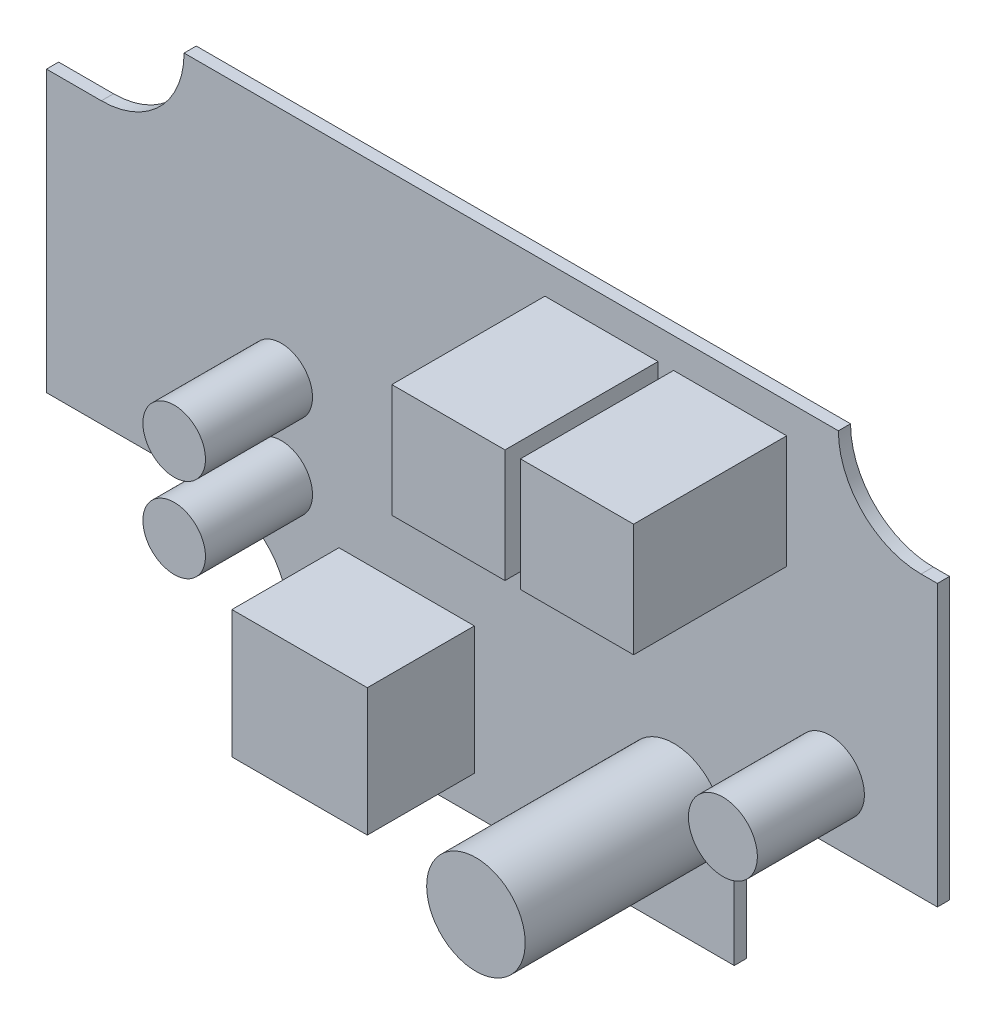
SolidWorks part; units mm, degrees
ref_plane "Front Plane" through (0, 0, 0) normal (0, 0, 1) x (1, 0, 0)
ref_plane "Top Plane" through (0, 0, 0) normal (0, 1, 0) x (1, 0, 0)
ref_plane "Right Plane" through (0, 0, 0) normal (1, 0, 0) x (0, 0, -1)
sketch "Sketch1" plane through (0, 0, 0) normal (0, 0, 1) x (1, 0, 0)
  line L0 (-42.3541, 30.2967) -> (-53.0616, 30.2967) construction
  line L1 (28.8729, -26.0779) -> (28.8729, -36.4043)
  line L2 (-38.257, -16.6937) -> (-60.1693, -16.6937)
  line L3 (-42.3541, 30.2967) -> (42.3541, 30.2967)
  line L4 (38.257, -16.6937) -> (55.1689, -16.6937)
  line L5 (-53.0616, 30.2967) -> (-53.0616, 19.5893) construction
  line L6 (-38.257, -16.6937) -> (-38.257, -26.0779) construction
  line L7 (-38.257, -26.0779) -> (-28.8729, -26.0779) construction
  line L8 (28.8729, -26.0779) -> (38.257, -26.0779) construction
  line L9 (38.257, -26.0779) -> (38.257, -16.6937) construction
  line L10 (53.0616, 19.5893) -> (53.0616, 30.2967) construction
  line L11 (53.0616, 30.2967) -> (42.3541, 30.2967) construction
  line L12 (55.1689, -16.6937) -> (55.1689, 19.5893)
  line L13 (-60.1693, -16.6937) -> (-60.1693, 19.5893)
  line L14 (-60.1693, 19.5893) -> (-53.0616, 19.5893)
  line L15 (55.1689, 19.5893) -> (53.0616, 19.5893)
  line L16 (28.8729, -36.4043) -> (-28.8729, -36.4043)
  line L17 (-28.8729, -36.4043) -> (-28.8729, -26.0779)
  line L18 (-62.1693, -33.1629) -> (-62.1693, 54.0037) construction
  line L19 (65.1689, -33.1629) -> (65.1689, 54.0037) construction
  line L20 (-55.9277, -40.4043) -> (55.9277, -40.4043) construction
  arc A0 (-42.3541, 30.2967) -> (-53.0616, 19.5893) centre (-53.0616, 30.2967) cw
  circle A1 centre (53.0616, 30.2967) radius 1.6 construction
  arc A2 (-38.257, -16.6937) -> (-28.8729, -26.0779) centre (-38.257, -26.0779) cw
  arc A3 (-33.2327, -26.0779) -> (-43.2814, -26.0779) centre (-38.257, -26.0779) ccw construction
  arc A4 (42.3541, 30.2967) -> (53.0616, 19.5893) centre (53.0616, 30.2967) ccw
  arc A5 (38.257, -16.6937) -> (28.8729, -26.0779) centre (38.257, -26.0779) ccw
  arc A6 (43.2814, -26.0779) -> (33.2327, -26.0779) centre (38.257, -26.0779) ccw construction
  circle A8 centre (-53.0616, 30.2967) radius 1.6 construction
  dimension "D1" = 2
  dimension "D2" = 9.3842
  dimension "D3" = 10.7075
  dimension "D4" = 10
  dimension "D5" = 4
extrude "Boss-Extrude1" add sketch "Sketch1" along normal blind 1.5748
sketch "Sketch2" plane through (0, 0, 1.5748) normal (0, 0, 1) x (1, 0, 0)
  line L1 (4.3619, 26.3914) -> (19.0119, 26.3914)
  line L2 (4.3619, 26.3914) -> (4.3619, 11.7414)
  line L3 (4.3619, 11.7414) -> (19.0119, 11.7414)
  line L4 (19.0119, 26.3914) -> (19.0119, 11.7414)
  line L5 (21.0119, 26.3914) -> (35.6619, 26.3914)
  line L6 (21.0119, 26.3914) -> (21.0119, 11.7414)
  line L7 (21.0119, 11.7414) -> (35.6619, 11.7414)
  line L8 (35.6619, 26.3914) -> (35.6619, 11.7414)
  dimension "D1" = 2
  dimension "D2" = 14.65
extrude "Boss-Extrude2" add sketch "Sketch2" along normal blind 19.82
sketch "Sketch3" plane through (0, 0, 1.5748) normal (0, 0, 1) x (1, 0, 0)
  circle A0 centre (21.0509, -21.7791) radius 6.38
  dimension "D1" = 12.76
extrude "Boss-Extrude3" add sketch "Sketch3" along normal blind 25.62
sketch "Sketch4" plane through (0, 0, 1.5748) normal (0, 0, 1) x (1, 0, 0)
  line L1 (-22.3027, -15.1438) -> (-4.7739, -15.1438)
  line L2 (-22.3027, -15.1438) -> (-22.3027, -31.671)
  line L3 (-22.3027, -31.671) -> (-4.7739, -31.671)
  line L4 (-4.7739, -15.1438) -> (-4.7739, -31.671)
  circle A0 centre (-29.7754, 0) radius 4.05
  circle A1 centre (-29.7754, -10.91) radius 4.05
  circle A2 centre (41.2613, -8.8411) radius 4.4585
  dimension "D1" = 8.1
  dimension "D2" = 16.5272
  dimension "D4" = 8.9169
  dimension "D3" = 17.5288
extrude "Boss-Extrude4" add sketch "Sketch4" along normal blind 13.86
